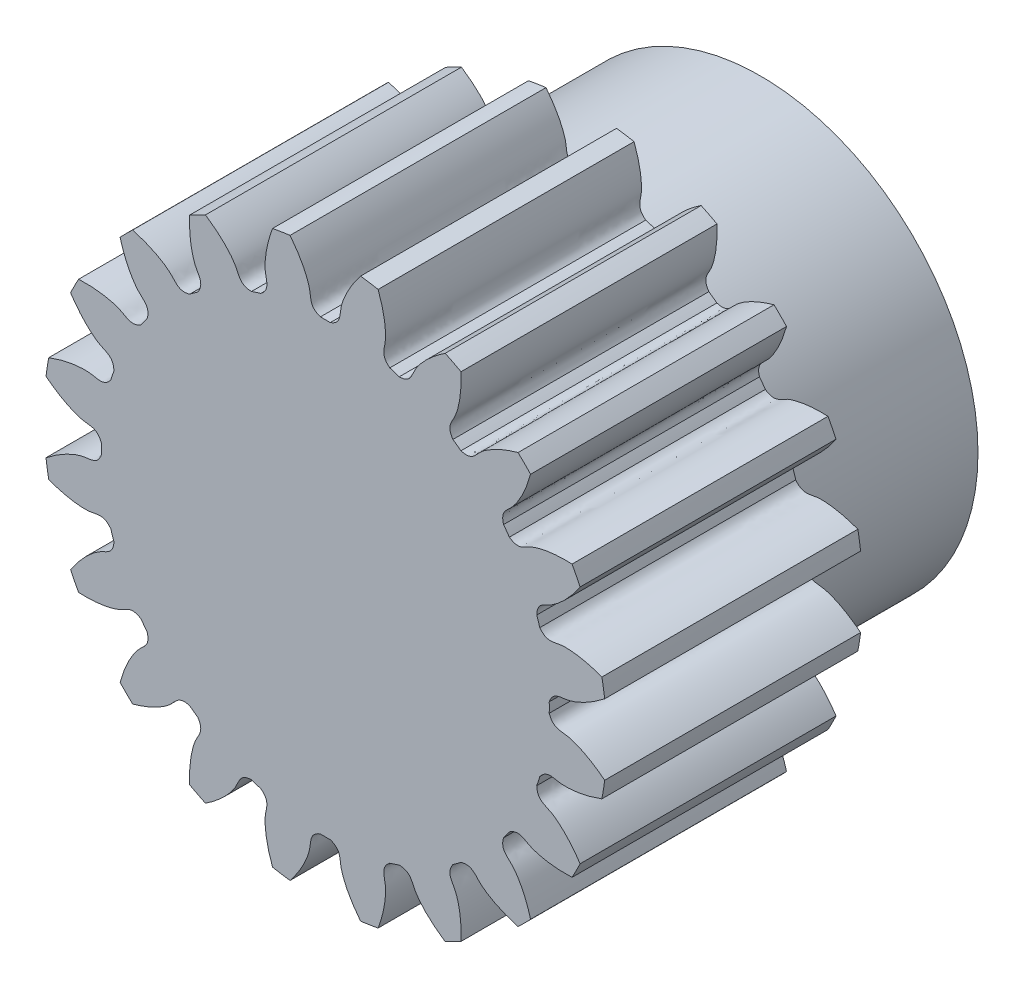
SolidWorks part; units mm, degrees
ref_plane "前视基准面" through (0, 0, 0) normal (0, 0, 1) x (1, 0, 0)
ref_plane "上视基准面" through (0, 0, 0) normal (0, 1, 0) x (1, 0, 0)
ref_plane "右视基准面" through (0, 0, 0) normal (1, 0, 0) x (0, 0, -1)
other "Configuration Table"
sketch "草图1" plane through (0, 0, 0) normal (0, 0, 1) x (1, 0, 0)
  circle A0 centre (0, 0) radius 22
extrude "凸台-拉伸1" add sketch "草图1" along normal blind 20
ref_axis "基准轴1" through (0, 0, -1.5) along (0, 0, 1)
sketch "草图2" plane through (0, 0, 0) normal (0, 0, 1) x (1, 0, 0)
  line L0 (0, 0) -> (0, 22) construction
  circle A0 centre (0, 0) radius 22 construction
  arc A1 (0.3866, 17.4957) -> (-0.3866, 17.4957) centre (0, 0) ccw
  arc A2 (6.3623, 24.9965) -> (-6.3623, 24.9965) centre (0, 0) ccw
  spline S0 degree 3 poles (0.3866, 17.4957) (1.2224, 17.787) (1.1142, 18.3742) (1.2258, 18.94) (1.2378, 18.9951) (1.2526, 19.0573) (1.2706, 19.1264) (1.292, 19.2024) (1.317, 19.2851) (1.3461, 19.3745) (1.3793, 19.4704) (1.4171, 19.5726) (1.4597, 19.6811) (1.5073, 19.7956) (1.5603, 19.9161) (1.6187, 20.0423) (1.683, 20.174) (1.7534, 20.3112) (1.83, 20.4535) (1.9132, 20.6008) (2.0031, 20.7529) (2.1, 20.9095) (2.204, 21.0705) (2.3155, 21.2356) (2.4346, 21.4046) (2.5615, 21.5772) (2.6964, 21.7533) (2.8395, 21.9324) (2.991, 22.1145) (3.1509, 22.2992) (3.3196, 22.4862) (3.4971, 22.6753) (3.6837, 22.8662) (3.8793, 23.0586) (4.0843, 23.2521) (4.2986, 23.4467) (4.5225, 23.6418) (4.7559, 23.8372) (4.9991, 24.0327) (5.2521, 24.2278) (5.515, 24.4223) (5.8829, 24.6833) (6.1679, 24.8727) (6.3623, 24.9965) knots 0 0 0 0 0.165916 0.170906 0.176664 0.183189 0.190482 0.198542 0.207371 0.216967 0.22733 0.238462 0.250361 0.263027 0.276462 0.290664 0.305634 0.321371 0.337876 0.355149 0.37319 0.391998 0.411574 0.431917 0.453028 0.474907 0.497554 0.520968 0.54515 0.570099 0.595817 0.622302 0.649554 0.677575 0.706363 0.735918 0.766242 0.797333 0.829191 0.861818 0.895212 0.929373 1 1 1 1
  spline S1 degree 3 poles (-0.3866, 17.4957) (-1.2224, 17.787) (-1.1142, 18.3742) (-1.2258, 18.94) (-1.2378, 18.9951) (-1.2526, 19.0573) (-1.2706, 19.1264) (-1.292, 19.2024) (-1.317, 19.2851) (-1.3461, 19.3745) (-1.3793, 19.4704) (-1.4171, 19.5726) (-1.4597, 19.6811) (-1.5073, 19.7956) (-1.5603, 19.9161) (-1.6187, 20.0423) (-1.683, 20.174) (-1.7534, 20.3112) (-1.83, 20.4535) (-1.9132, 20.6008) (-2.0031, 20.7529) (-2.1, 20.9095) (-2.204, 21.0705) (-2.3155, 21.2356) (-2.4346, 21.4046) (-2.5615, 21.5772) (-2.6964, 21.7533) (-2.8395, 21.9324) (-2.991, 22.1145) (-3.1509, 22.2992) (-3.3196, 22.4862) (-3.4971, 22.6753) (-3.6837, 22.8662) (-3.8793, 23.0586) (-4.0843, 23.2521) (-4.2986, 23.4467) (-4.5225, 23.6418) (-4.7559, 23.8372) (-4.9991, 24.0327) (-5.2521, 24.2278) (-5.515, 24.4223) (-5.8829, 24.6833) (-6.1679, 24.8727) (-6.3623, 24.9965) knots 0 0 0 0 0.165916 0.170906 0.176664 0.183189 0.190482 0.198542 0.207371 0.216967 0.22733 0.238462 0.250361 0.263027 0.276462 0.290664 0.305634 0.321371 0.337876 0.355149 0.37319 0.391998 0.411574 0.431917 0.453028 0.474907 0.497554 0.520968 0.54515 0.570099 0.595817 0.622302 0.649554 0.677575 0.706363 0.735918 0.766242 0.797333 0.829191 0.861818 0.895212 0.929373 1 1 1 1
extrude "切除-拉伸1" cut sketch "草图2" along normal through all
pattern_circular "阵列(圆周)1" count 20 every 18 about axis through (0, 0, -1.5) along (0, 0, 1) of "切除-拉伸1"
sketch "草图3" plane through (0, 0, 0) normal (0, 0, 1) x (1, 0, 0)
  circle A0 centre (0, 0) radius 20 construction
  dimension "Dn" = 40
sketch "草图4" plane through (0, 0, 0) normal (0, 0, -1) x (-1, 0, 0)
  circle A0 centre (0, 0) radius 17
  dimension "D1" = 34
extrude "凸台-拉伸2" add sketch "草图4" along normal blind 14
sketch "草图5" plane through (0, 0, -14) normal (0, 0, -1) x (-1, 0, 0)
  circle A0 centre (0, 0) radius 3
  dimension "D1" = 6
extrude "切除-拉伸2" cut sketch "草图5" against normal blind 14
